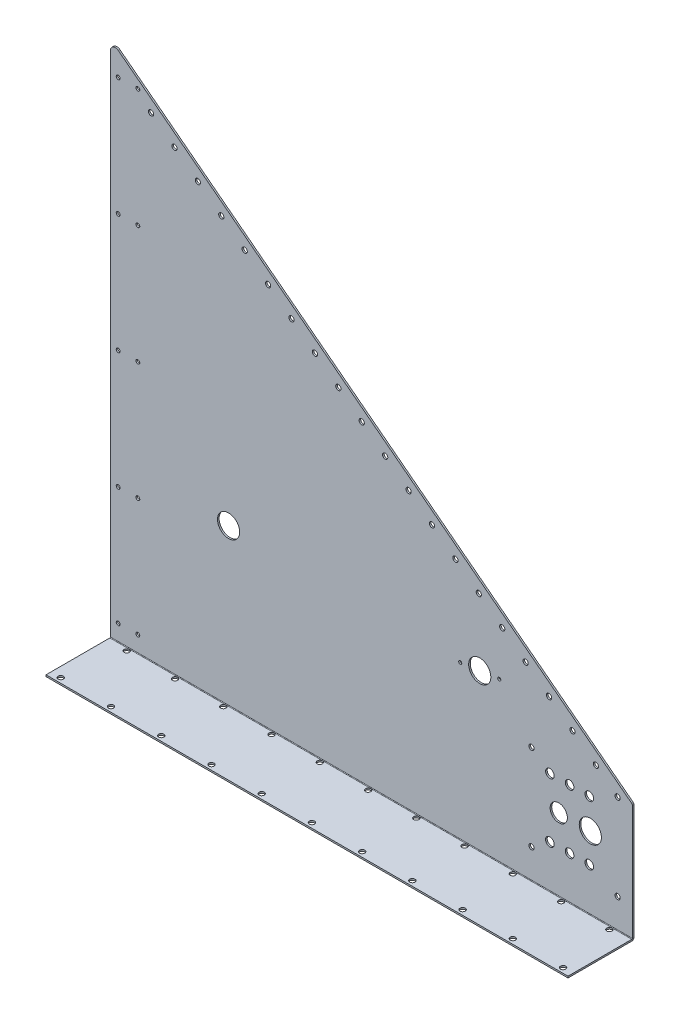
SolidWorks part; units mm, degrees
note: The reader was unsure of these and kept them because the rebuilt part matched: flange length of "Edge-Flange1".
ref_plane "Front Plane" through (0, 0, 0) normal (0, 0, 1) x (1, 0, 0)
ref_plane "Top Plane" through (0, 0, 0) normal (0, 1, 0) x (1, 0, 0)
ref_plane "Right Plane" through (0, 0, 0) normal (1, 0, 0) x (0, 0, -1)
sketch "Sketch1" plane through (0, 0, 0) normal (0, 0, 1) x (1, 0, 0)
  line L0 (-279.2723, -371.8339) -> (-279.2723, 285.9358)
  line L1 (393.8277, -371.8339) -> (393.8277, -219.4339)
  line L2 (-279.2723, -371.8339) -> (393.8277, -371.8339)
  line L3 (393.8277, -219.4339) -> (-268.4322, 290.426)
  arc A0 (-279.2723, 285.9358) -> (-268.4322, 290.426) centre (-272.9223, 285.9358) cw
  point P5 (393.8277, 301.2661)
  point P6 (-279.2723, 301.2661)
  dimension "D3" = 673.1
  dimension "D2" = 6.35
  dimension "D1" = 673.1
  dimension "D4" = 152.4
base flange "Base-Flange1" sketch "Sketch1" thickness 2.0523 reverse thickness direction no parameters "D1"=0.7366
edge flange "Edge-Flange1" sketch "Sketch8" flange angle 90 flange length 85.09 flange position material inside bend radius 0.7366 thickness 2.0523 relief rectangular parameters "D6"=10
sketch "Sketch8" plane through (0, -371.8339, 0) normal (0, -1, 0) x (1, 0, 0)
  line L0 (-279.2723, 0) -> (393.8277, 0) construction
  line L1 (-279.2723, 0) -> (393.8277, 0)
  line L2 (-279.2723, 0) -> (-279.2723, 83.0377)
  line L3 (-279.2723, 83.0377) -> (393.8277, 83.0377)
  line L4 (393.8277, 83.0377) -> (393.8277, 0)
bend "EdgeBend1" bend radius 0.7366 bend angle 90 parameters "D5"=1
sketch "Sketch9" plane through (0, -369.7816, 0) normal (0, 1, 0) x (1, 0, 0)
  line L0 (393.8277, -0.7366) -> (393.8277, -83.0377) construction
  line L1 (393.8277, -83.0377) -> (-279.2723, -83.0377) construction
  line L2 (393.8277, 2.0523) -> (-279.2723, 2.0523) construction
  circle A0 centre (381.1277, -76.6877) radius 3.3782
  circle A1 centre (316.3577, -76.6877) radius 3.3782
  circle A2 centre (251.5877, -76.6877) radius 3.3782
  circle A3 centre (186.8177, -76.6877) radius 3.3782
  circle A4 centre (122.0477, -76.6877) radius 3.3782
  circle A5 centre (57.2777, -76.6877) radius 3.3782
  circle A6 centre (-7.4923, -76.6877) radius 3.3782
  circle A7 centre (-72.2623, -76.6877) radius 3.3782
  circle A8 centre (-137.0323, -76.6877) radius 3.3782
  circle A9 centre (-201.8023, -76.6877) radius 3.3782
  circle A10 centre (-266.5723, -76.6877) radius 3.3782
  circle A11 centre (368.4277, -4.2977) radius 3.3782
  circle A12 centre (306.1977, -4.2977) radius 3.3782
  circle A13 centre (243.9677, -4.2977) radius 3.3782
  circle A14 centre (181.7377, -4.2977) radius 3.3782
  circle A15 centre (119.5077, -4.2977) radius 3.3782
  circle A16 centre (57.2777, -4.2977) radius 3.3782
  circle A17 centre (-4.9523, -4.2977) radius 3.3782
  circle A18 centre (-67.1823, -4.2977) radius 3.3782
  circle A19 centre (-129.4123, -4.2977) radius 3.3782
  circle A20 centre (-191.6423, -4.2977) radius 3.3782
  circle A21 centre (-253.8723, -4.2977) radius 3.3782
  dimension "D1" = 6.7564
  dimension "D5" = 6.7564
  dimension "D6" = 6.35
  dimension "D2" = 12.7
  dimension "D3" = 6.35
  dimension "D7" = 25.4
  dimension "D4" = 11
  dimension "D8" = 11
extrude "Cut-Extrude1" cut sketch "Sketch9" against normal blind 2.54 normal cut yes
sketch "Sketch10" plane through (0, -369.7816, 0) normal (0, 1, 0) x (1, 0, 0)
sketch "Sketch11" plane through (0, 0, 0) normal (0, 0, 1) x (1, 0, 0)
  line L0 (-279.2723, 285.9358) -> (-279.2723, -369.045) construction
  circle A0 centre (-269.2723, 260.7995) radius 2.5
  circle A1 centre (-269.2723, 108.3995) radius 2.5
  circle A2 centre (-269.2723, -44.0005) radius 2.5
  circle A3 centre (-269.2723, -196.4005) radius 2.5
  circle A4 centre (-269.2723, -348.8005) radius 2.5
  arc A5 (-268.4322, 290.426) -> (-279.2723, 285.9358) centre (-272.9223, 285.9358) ccw construction
  circle A6 centre (-243.8723, 260.7995) radius 2.5
  circle A7 centre (-243.8723, 108.3995) radius 2.5
  circle A8 centre (-243.8723, -44.0005) radius 2.5
  circle A9 centre (-243.8723, -196.4005) radius 2.5
  circle A10 centre (-243.8723, -348.8005) radius 2.5
  dimension "D2" = 5
  dimension "D3" = 10
  dimension "D1" = 25.4
  dimension "D4" = 5
  dimension "D5" = 2
extrude "Cut-Extrude2" cut sketch "Sketch11" against normal blind 2.54 normal cut yes
sketch "Sketch12" plane through (0, 0, -2.0523) normal (0, 0, -1) x (-1, 0, 0)
  circle A0 centre (-374.7777, -220.7955) radius 3.3782 construction
  circle A1 centre (-374.7777, -331.9205) radius 3.3782 construction
  circle A2 centre (-263.6527, -331.9205) radius 3.3782 construction
  circle A3 centre (-263.6527, -220.7955) radius 3.3782 construction
  circle A5 centre (-196.9777, -168.6339) radius 14.2875 construction
  circle A7 centre (126.8723, -168.6339) radius 14.2875 construction
  circle A8 centre (-374.7777, -220.7955) radius 3.3782
  circle A9 centre (-374.7777, -331.9205) radius 3.3782
  circle A10 centre (-263.6527, -331.9205) radius 3.3782
  circle A11 centre (-263.6527, -220.7955) radius 3.3782
  circle A12 centre (-222.1657, -165.3589) radius 2.0193 construction
  circle A13 centre (-196.9777, -168.6339) radius 14.2875
  circle A14 centre (-171.7897, -171.9089) radius 2.0193 construction
  circle A15 centre (126.8723, -168.6339) radius 14.2875
  circle A16 centre (-222.1657, -165.3589) radius 2.0193
  circle A17 centre (-171.7897, -171.9089) radius 2.0193
extrude "Cut-Extrude3" cut sketch "Sketch12" against normal blind 2.54 normal cut yes
fillet "Fillet1" radius 2.54 1 edges at (393.8277, -219.4339, -1.0262)
sketch "Sketch13" plane through (0, 0, -2.0523) normal (0, 0, -1) x (-1, 0, 0)
  circle A0 centre (-287.4652, -314.5662) radius 5.5626 construction
  circle A1 centre (-312.8652, -314.5662) radius 5.5626 construction
  circle A2 centre (-338.2652, -314.5662) radius 5.5626 construction
  circle A3 centre (-298.8698, -276.358) radius 11.1125 construction
  circle A4 centre (-339.5606, -276.358) radius 14.2875 construction
  circle A5 centre (-287.4652, -238.1497) radius 5.5626 construction
  circle A6 centre (-312.8652, -238.1497) radius 5.5626 construction
  circle A7 centre (-338.2652, -238.1497) radius 5.5626 construction
  circle A8 centre (-287.4652, -314.5662) radius 5.5626
  circle A9 centre (-312.8652, -314.5662) radius 5.5626
  circle A10 centre (-338.2652, -314.5662) radius 5.5626
  circle A11 centre (-298.8698, -276.358) radius 11.1125
  circle A12 centre (-339.5606, -276.358) radius 14.2875
  circle A13 centre (-287.4652, -238.1497) radius 5.5626
  circle A14 centre (-312.8652, -238.1497) radius 5.5626
  circle A15 centre (-338.2652, -238.1497) radius 5.5626
extrude "Cut-Extrude4" cut sketch "Sketch13" against normal blind 2.54 normal cut yes
sketch "Sketch14" plane through (0, 0, 0) normal (0, 0, 1) x (1, 0, 0)
  line L0 (392.8372, -218.6713) -> (-268.4322, 290.426) construction
  circle A0 centre (-226.8803, 242.4083) radius 3.3782
  circle A1 centre (-196.6908, 219.166) radius 3.3782
  circle A2 centre (-166.5013, 195.9238) radius 3.3782
  circle A3 centre (-136.3118, 172.6815) radius 3.3782
  circle A4 centre (-106.1222, 149.4392) radius 3.3782
  circle A5 centre (-75.9327, 126.197) radius 3.3782
  circle A6 centre (-45.7432, 102.9547) radius 3.3782
  circle A7 centre (-15.5537, 79.7124) radius 3.3782
  circle A8 centre (14.6358, 56.4702) radius 3.3782
  circle A9 centre (44.8253, 33.2279) radius 3.3782
  circle A10 centre (75.0149, 9.9856) radius 3.3782
  circle A11 centre (105.2044, -13.2567) radius 3.3782
  circle A12 centre (135.3939, -36.4989) radius 3.3782
  circle A13 centre (165.5834, -59.7412) radius 3.3782
  circle A14 centre (195.7729, -82.9835) radius 3.3782
  circle A15 centre (225.9624, -106.2257) radius 3.3782
  circle A16 centre (256.1519, -129.468) radius 3.3782
  circle A17 centre (286.3415, -152.7103) radius 3.3782
  circle A18 centre (316.531, -175.9525) radius 3.3782
  circle A19 centre (346.7205, -199.1948) radius 3.3782
  dimension "D1" = 6.7564
  dimension "D2" = 12.7
  dimension "D3" = 63.5
  dimension "D4" = 20
extrude "Cut-Extrude5" cut sketch "Sketch14" against normal blind 2.54 normal cut yes
sketch "Bend-Lines1" plane through (0, 0, 0) normal (0, 1, 0) x (1, 0, 0)
sketch "Bounding-Box1" plane through (0, 0, 0) normal (0, 1, 0) x (1, 0, 0)
sheet metal parameters "Sheet-Metal1" thickness 2.0523 parameters "D1"=0.7366
flat pattern "Flat-Pattern1" [suppressed]
sketch "Bend-Lines2" plane through (0, 0, 0) normal (0, 1, 0) x (1, 0, 0)
sketch "Bounding-Box2" [suppressed] plane through (0, 0, 0) normal (0, 1, 0) x (1, 0, 0)
sheet metal parameters "Sheet-Metal2" thickness 2.0523 parameters "D1"=0.7366
flat pattern "Flat-Pattern1" [suppressed]
sketch "Bend-Lines2" plane through (0, 0, 0) normal (0, 1, 0) x (1, 0, 0)
sketch "Bounding-Box2" [suppressed] plane through (0, 0, 0) normal (0, 1, 0) x (1, 0, 0)
bend of the flat pattern "Flatten-<EdgeBend1>1"
sheet metal parameters "Sheet-Metal3" thickness 2.0523 parameters "D1"=0.7366
flat pattern "Flat-Pattern1" [suppressed]
sketch "Bend-Lines2" plane through (0, 0, 0) normal (0, 1, 0) x (1, 0, 0)
sketch "Bounding-Box2" [suppressed] plane through (0, 0, 0) normal (0, 1, 0) x (1, 0, 0)
bend of the flat pattern "Flatten-<EdgeBend1>1"
sheet metal parameters "Sheet-Metal4" thickness 2.0523 parameters "D1"=0.7366
flat pattern "Flat-Pattern1" [suppressed]
sketch "Bend-Lines2" plane through (0, 0, 0) normal (0, 1, 0) x (1, 0, 0)
sketch "Bounding-Box2" [suppressed] plane through (0, 0, 0) normal (0, 1, 0) x (1, 0, 0)
bend of the flat pattern "Flatten-<EdgeBend1>1"
sheet metal parameters "Sheet-Metal5" thickness 2.0523 parameters "D1"=0.7366
flat pattern "Flat-Pattern1" [suppressed]
sketch "Bend-Lines2" plane through (0, 0, 0) normal (0, 1, 0) x (1, 0, 0)
sketch "Bounding-Box2" [suppressed] plane through (0, 0, 0) normal (0, 1, 0) x (1, 0, 0)
bend of the flat pattern "Flatten-<EdgeBend1>1"
sheet metal parameters "Sheet-Metal6" thickness 2.0523 parameters "D1"=0.7366
flat pattern "Flat-Pattern1" [suppressed]
sketch "Bend-Lines2" plane through (0, 0, 0) normal (0, 1, 0) x (1, 0, 0)
sketch "Bounding-Box2" [suppressed] plane through (0, 0, 0) normal (0, 1, 0) x (1, 0, 0)
bend of the flat pattern "Flatten-<EdgeBend1>1"
sheet metal parameters "Sheet-Metal7" thickness 2.0523 parameters "D1"=0.7366
flat pattern "Flat-Pattern1" [suppressed]
sketch "Bend-Lines2" plane through (0, 0, 0) normal (0, 1, 0) x (1, 0, 0)
sketch "Bounding-Box2" [suppressed] plane through (0, 0, 0) normal (0, 1, 0) x (1, 0, 0)
bend of the flat pattern "Flatten-<EdgeBend1>1"
